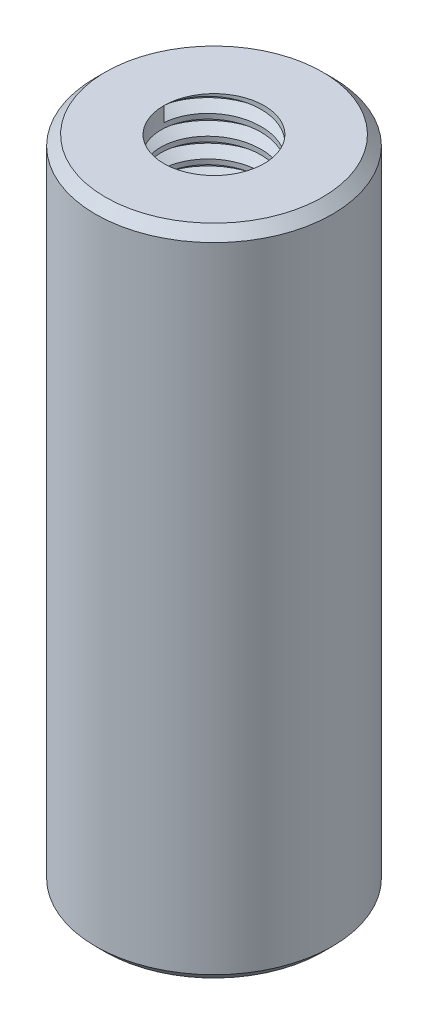
SolidWorks part; units mm, degrees
material "6061-T6 (SS)"
ref_plane "Alzado" through (0, 0, 0) normal (0, 0, 1) x (1, 0, 0)
ref_plane "Planta" through (0, 0, 0) normal (0, 1, 0) x (1, 0, 0)
ref_plane "Vista lateral" through (0, 0, 0) normal (1, 0, 0) x (0, 0, -1)
sketch "Croquis2" plane through (0, 0, 0) normal (0, 1, 0) x (1, 0, 0)
  circle A0 centre (0, 0) radius 4.7625
  dimension "D1" = 9.525
extrude "Saliente-Extruir1" add sketch "Croquis2" along normal mid plane 26.3017
chamfer "Chaflán1" distance 0.3969 angle 45 2 edges at (0, -13.1509, 4.7625) (0, 13.1509, 4.7625)
sketch "Croquis3" plane through (0, 0, 0) normal (0, 1, 0) x (1, 0, 0)
  circle A0 centre (0, 0) radius 2.0193
  dimension "D1" = 4.0386
extrude "Tap Hole 1" cut sketch "Croquis3" against normal blind 9.525 from surface starting at face at (0, 13.1509, 4.3656)
extrude "Tap Hole 2" cut sketch "Croquis3<2>" along normal blind 9.525 from surface starting at face at (0, -13.1509, 4.3656)
sketch "Croquis3<2>" plane through (0, 0, 0) normal (0, 1, 0) x (1, 0, 0) same geometry as "Croquis3"
sketch "Croquis4" plane through (0, 0, 0) normal (0, 1, 0) x (1, 0, 0)
  circle A0 centre (0, 0) radius 2.4892
  dimension "D1" = 4.9784
extrude "Clearance Hole" [suppressed] cut sketch "Croquis4" against normal through all both and the other way through all
thread "Rosca1" pitch 0.7937 method cut profile "Perfil de rosca1" start angle 0, offset 0, length 0, pitch 0.7937, diameter 4.0386
ref_plane "Plano1" through (-2.0193, 13.1509, 0) normal (0, 0, 1) x (-1, 0, 0)
sketch "Perfil de rosca1" plane through (-2.0193, 13.1509, 0) normal (0, 0, 1) x (-1, 0, 0)
  line L0 (0, 0) -> (0, 0.7937) construction
  line L1 (0, 0) -> (0.4296, 0.248)
  line L2 (0.4296, 0.248) -> (0.4296, 0.3473)
  line L3 (0.4296, 0.3473) -> (0, 0.5953)
  line L4 (0.4296, 0.2977) -> (0, 0.2977) construction
  line L11 (0, 0) -> (0, 0.5953)
  point P2 (0, 0)
  dimension "Pitch" = 0.7937
  dimension "Profile_Angle" = 60
  dimension "Profile_Land" = 0.0992
  dimension "Profile_Height" = 0.4296
thread "Rosca2" pitch 0.7937 method cut profile "Perfil de rosca2" start angle 0, offset 0, length 0, pitch 0.7937, diameter 4.0386
ref_plane "Plano2" through (2.0193, -13.1509, 0) normal (0, 0, 1) x (1, 0, 0)
sketch "Perfil de rosca2" plane through (2.0193, -13.1509, 0) normal (0, 0, 1) x (1, 0, 0)
  line L0 (0, 0) -> (0, 0.7937) construction
  line L1 (0, 0) -> (0.4296, 0.248)
  line L2 (0.4296, 0.248) -> (0.4296, 0.3473)
  line L3 (0.4296, 0.3473) -> (0, 0.5953)
  line L4 (0.4296, 0.2977) -> (0, 0.2977) construction
  line L11 (0, 0) -> (0, 0.5953)
  point P2 (0, 0)
  dimension "Pitch" = 0.7937
  dimension "Profile_Angle" = 60
  dimension "Profile_Land" = 0.0992
  dimension "Profile_Height" = 0.4296
equation "\"OD\"= 0.375pulgadas"
equation "\"Largo\"= 1.0355pulgadas"
equation "\"Tap Hole\"= IIF ( \"OD\" = 0.375pulgadas , 0.1590pulgadas , 0.201pulgadas )"
equation "\"Spacer Hole\"= IIF ( \"OD\" = 0.375pulgadas , 0.196pulgadas , 0.257pulgadas )"
equation "\"D1@Croquis2\"=\"OD\""
equation "\"D1@Saliente-Extruir1\"=\"Largo\""
equation "\"D1@Croquis3\"=\"Tap Hole\""
equation "\"D1@Croquis4\"=\"Spacer Hole\""
